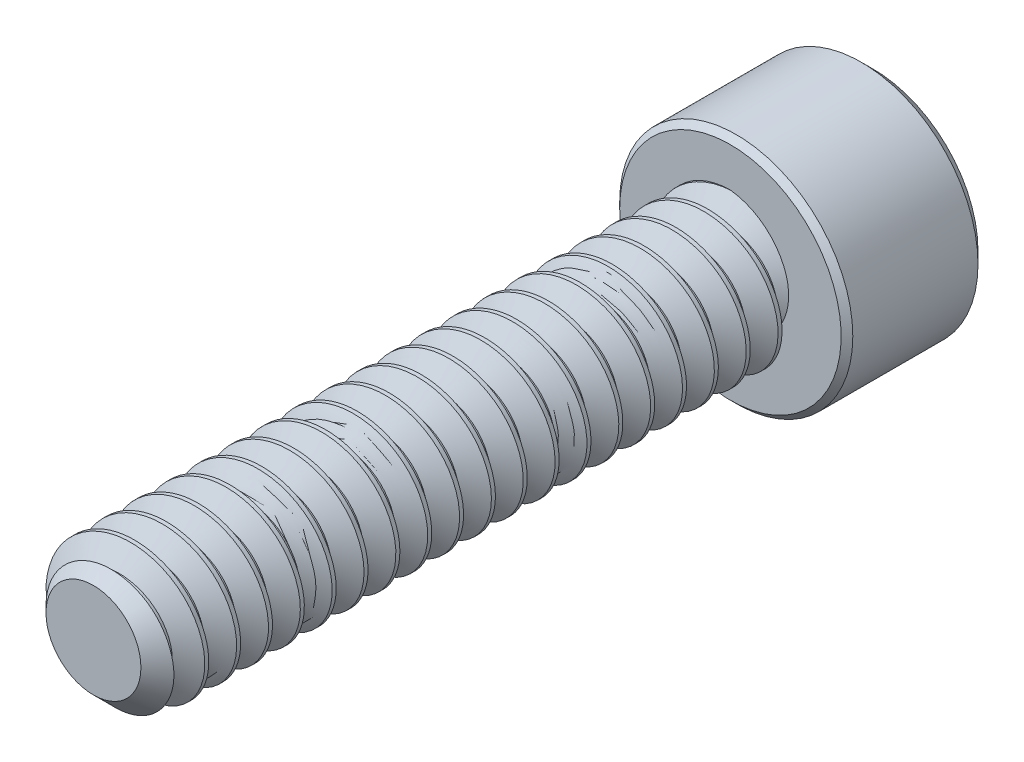
SolidWorks part; units mm, degrees
material "Cast Stainless Steel"
ref_plane "Front Plane" through (0, 0, 0) normal (0, 0, 1) x (1, 0, 0)
ref_plane "Top Plane" through (0, 0, 0) normal (0, 1, 0) x (1, 0, 0)
ref_plane "Right Plane" through (0, 0, 0) normal (1, 0, 0) x (0, 0, -1)
sketch "Sketch0" plane through (0, 0, 0) normal (1, 0, 0) x (0, 0, -1)
  line L0 (0, 0) -> (12.7, 0) construction
  point P2 (15.5448, 0)
  point P4 (0, 0)
  dimension "D1" = 12.7
  dimension "D2" = 2.8448
  dimension "Min Thread" = 0
sketch "Sketch1" plane through (0, 0, 0) normal (0, 0, 1) x (1, 0, 0)
  circle A0 centre (0, 0) radius 1.4224
  dimension "OD" = 2.8448
extrude "Extrude1" add sketch "Sketch1" against normal blind 12.7
sketch "Sketch2" plane through (0, 0, 0) normal (0, 0, 1) x (1, 0, 0)
  circle A0 centre (0, 0) radius 1.4224 construction
  circle A1 centre (0, 0) radius 1.4224
curve "Helix/Spiral1" pitch 0.635 height 13.335 radius 1.4224 centre (0, 0, 0) axis (0, 0, -1) start towards (0, 1, 0) parameters "pitch"=0.635
chamfer "Chamfer3" distance 0.4763 angle 45 1 edges at (1.4224, 0, 0)
sketch "Sketch3" plane through (0, 0, 0) normal (1, 0, 0) x (0, 0, -1)
  line L0 (-0.5556, 1.4224) -> (-0.3175, 1.01)
  line L1 (-0.3175, 1.01) -> (-0.2381, 1.01)
  line L2 (-0.2381, 1.01) -> (0, 1.4224)
  line L3 (-0.5556, 1.4224) -> (0, 1.4224)
  line L4 (-0.2778, 1.4224) -> (-0.2778, 1.01) construction
  line L5 (-0.4366, 1.2162) -> (-0.1191, 1.2162) construction
  line L6 (0, 1.4224) -> (0, -1.4224) construction
  dimension "D1" = 0.0794
  dimension "D2" = 0.3175
  dimension "D3" = 60
sweep "Cut-Sweep1" cut profiles "Sketch3" path "Helix/Spiral1"
sketch "Sketch5" plane through (0, 0, 0) normal (1, 0, 0) x (0, 0, -1)
  line L0 (12.7, -1.0232) -> (12.7, 1.0149) construction
  line L1 (12.7, 1.4224) -> (0, 1.4224)
  line L2 (12.7, 1.4224) -> (12.7, 0)
  line L3 (12.7, 0) -> (-0.5177, 0)
  line L4 (0, 0) -> (12.7, 0) construction
  line L5 (0, 1.4224) -> (-0.5177, 0)
  line L6 (0, 0) -> (15.24, 0) construction
  dimension "D1" = 70
  dimension "D3" = 2.54
revolve "partially thread" [suppressed] add sketch "Sketch5" angle 360 about L6
sketch "Sketch6" plane through (0, 0, -12.7) normal (0, 0, -1) x (-1, 0, 0)
  circle A0 centre (0, 0) radius 2.3241
  dimension "head dia" = 4.6482
extrude "Extrude2" add sketch "Sketch6" along normal blind 2.8448
sketch "Sketch7" plane through (0, 0, -15.5448) normal (0, 0, -1) x (-1, 0, 0)
  line L1 (0, 1.3748) -> (-1.1906, 0.6874)
  line L2 (-1.1906, 0.6874) -> (-1.1906, -0.6874)
  line L3 (-1.1906, -0.6874) -> (0, -1.3748)
  line L4 (0, -1.3748) -> (1.1906, -0.6874)
  line L5 (1.1906, -0.6874) -> (1.1906, 0.6874)
  line L6 (1.1906, 0.6874) -> (0, 1.3748)
  circle A0 centre (0, 0) radius 1.1906 construction
  dimension "hex dia" = 2.3813
extrude "Cut-Extrude1" cut sketch "Sketch7" against normal blind 1.7859
sketch "Sketch8" plane through (0, 0, -15.5448) normal (0, 0, -1) x (-1, 0, 0)
  circle A0 centre (0, 0) radius 1.3748
extrude "Cut-Extrude2" cut sketch "Sketch8" against normal through all draft 45
chamfer "Chamfer1" distance 0.2324 angle 45 1 edges at (-2.3241, 0, -15.5448)
chamfer "Chamfer2" distance 0.1162 angle 45 1 edges at (-2.3241, 0, -12.7)
sketch "Sketch9" plane through (0, 0, 0) normal (1, 0, 0) x (0, 0, -1)
  line L0 (0, 1.4224) -> (0, -1.4224) construction
  line L1 (1.5875, 1.4224) -> (1.5875, -1.4224) construction
  line L2 (15.5448, 2.3241) -> (15.5448, -2.3241) construction
  line L3 (12.7, 2.3241) -> (12.7, -2.3241) construction
  line L4 (12.7, 2.2079) -> (12.7, -2.2079) construction
  line L5 (15.5448, -2.0917) -> (15.5448, 2.0917) construction
  line L6 (12.7, -2.3241) -> (12.7, 2.3241) construction
  line L7 (0, 0.9462) -> (0, -0.9462) construction
  line L8 (-0.5556, 1.4224) -> (0, 1.4224) construction
  line L9 (1.5875, 0) -> (0, 0) construction
  dimension "D1" = 1.5875
equation "\"D3@Helix/Spiral1\" = \"screw length@Extrude1\"+\"pitch@Helix/Spiral1\""
equation "\"D1@Sketch3\" = \"pitch@Helix/Spiral1\"*.125"
equation "\"D2@Sketch3\" = \"pitch@Helix/Spiral1\"*.5"
equation "\"D1@Cut-Extrude1\" = \"hex dia@Sketch7\"*.75"
equation "\"D1@Chamfer1\" = \"head dia@Sketch6\"*.05"
equation "\"D1@Sketch9\" = \"pitch@Helix/Spiral1\"*2.50"
equation "\"D1@Chamfer2\" = \"D1@Chamfer1\"/2"
equation "\"D1@Chamfer3\" = \"pitch@Helix/Spiral1\"*.750"
equation "\"D1@Sketch0\" = \"screw length@Extrude1\""
equation "\"D2@Sketch0\" = \"head depth@Extrude2\""
